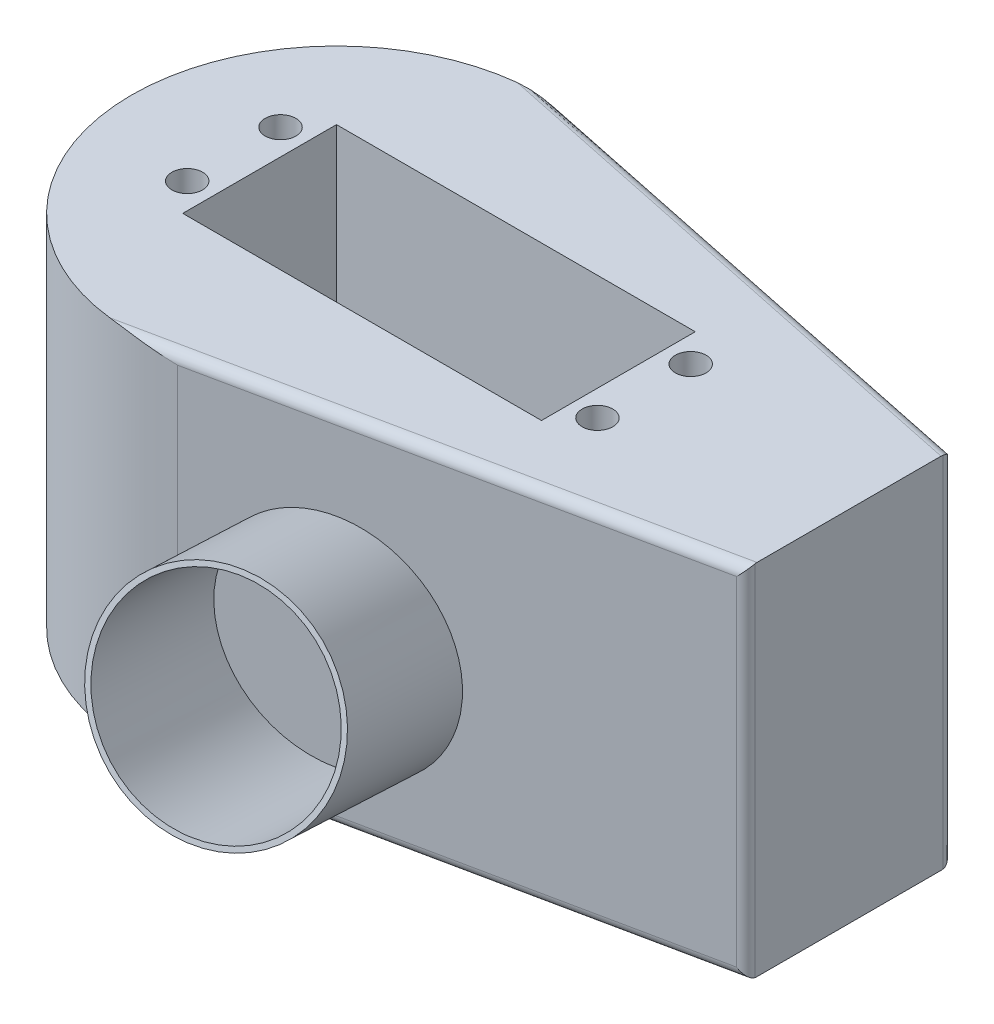
SolidWorks part; units mm, degrees
note: The reader was unsure of these and kept them because the rebuilt part matched: shared geometry of "Sketch3<3>".
material "ABS"
ref_plane "Front Plane" through (0, 0, 0) normal (0, 0, 1) x (1, 0, 0)
ref_plane "Top Plane" through (0, 0, 0) normal (0, 1, 0) x (1, 0, 0)
ref_plane "Right Plane" through (0, 0, 0) normal (1, 0, 0) x (0, 0, -1)
sketch "Sketch1" plane through (0, 0, 0) normal (0, 1, 0) x (1, 0, 0)
  line L0 (0, 0) -> (50, 0) construction
  line L1 (50, 10) -> (50, -10)
  line L2 (4.0843, 19.5785) -> (50, 10)
  line L3 (50, -10) -> (4.0843, -19.5785)
  arc A0 (4.0843, 19.5785) -> (4.0843, -19.5785) centre (0, 0) ccw
  point P3 (50, 0)
  dimension "D1" = 20
  dimension "D2" = 50
  dimension "D3" = 20
extrude "Boss-Extrude1" add sketch "Sketch1" along normal blind 35
sketch "Sketch2" plane through (0, 35, 0) normal (0, 1, 0) x (1, 0, 0)
  line L0 (0, 0) -> (-7.5, 0) construction
  line L1 (-7.5, 7.5) -> (27.5, 7.5)
  line L2 (-7.5, 7.5) -> (-7.5, -7.5)
  line L3 (-7.5, -7.5) -> (27.5, -7.5)
  line L4 (27.5, 7.5) -> (27.5, -7.5)
  dimension "D1" = 15
  dimension "D2" = 35
  dimension "D3" = 7.5
extrude "Cut-Extrude1" cut sketch "Sketch2" against normal blind 15
fillet "Fillet1" radius 1 6 edges at (50, 17.5, -10) (27.0421, 35, -14.7893) (27.0421, 0, -14.7893) (27.0421, 35, 14.7893) (50, 17.5, 10) (27.0421, 0, 14.7893)
sketch "Sketch3" plane through (0, 0, 0) normal (0, -1, 0) x (1, 0, 0)
  circle A0 centre (0, 0) radius 7.5
  circle A1 centre (0, 0) radius 3
  dimension "D1" = 15
  dimension "D2" = 6
extrude "Cut-Extrude2" cut sketch "Sketch3" against normal blind 10 contours A1 | A0 A1
extrude "Cut-Extrude3" cut sketch "Sketch3<3>" against normal through all contours A1
sketch "Sketch3<3>" plane through (0, 0, 0) normal (0, -1, 0) x (1, 0, 0) same geometry as "Sketch3"
ref_plane "Plane1" through (0, 4.431, 15.9775) normal (0, 0.2672, 0.9636) x (1, 0, 0)
sketch "Sketch4" plane through (0, 4.431, 15.9775) normal (0, 0.2672, 0.9636) x (1, 0, 0)
  line L0 (17, 0) -> (17, 25) construction
  dimension "D1" = 17
  dimension "D2" = 25
ref_plane "Plane2" through (4.5101, 5.204, 18.765) normal (0.2256, 0.2603, 0.9388) x (0, 0.9636, -0.2672)
sketch "Sketch5" plane through (4.5101, 5.204, 18.765) normal (0.2256, 0.2603, 0.9388) x (0, 0.9636, -0.2672)
  circle A0 centre (10.36, -11.75) radius 10
  dimension "D1" = 20
  dimension "D2" = 11.75
  dimension "D3" = 10.36
extrude "Extrude-Thin1" add sketch "Sketch5" along normal blind 20 thin
sketch "Sketch6" plane through (0, 35, 0) normal (0, 1, 0) x (1, 0, 0)
  line L0 (-7.5, 7.5) -> (-7.5, -7.5) construction
  line L1 (27.5, 7.5) -> (-7.5, 7.5) construction
  line L2 (10, 7.5) -> (10, -7.5) construction
  line L3 (27.5, 7.5) -> (-7.5, 7.5) construction
  line L4 (-7.5, -7.5) -> (27.5, -7.5) construction
  line L5 (-19.8375, 0) -> (19.8375, 0) construction
  circle A0 centre (-10.01, 4.55) radius 1.5
  circle A1 centre (-10.01, -4.55) radius 1.5
  circle A2 centre (30.01, -4.55) radius 1.5
  circle A3 centre (30.01, 4.55) radius 1.5
  dimension "D1" = 3
  dimension "D2" = 2.51
  dimension "D3" = 2.95
extrude "Cut-Extrude4" cut sketch "Sketch6" against normal blind 8.2
